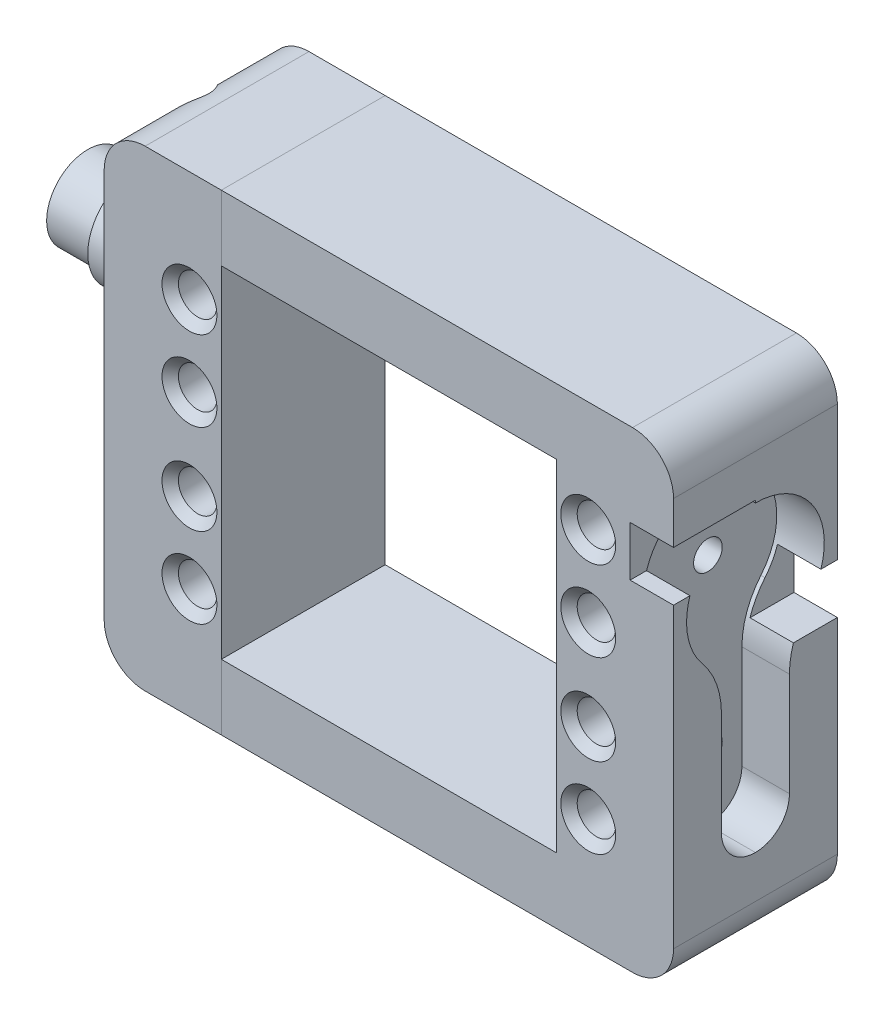
SolidWorks part; units mm, degrees
material "ABS"
ref_plane "Front Plane" through (0, 0, 0) normal (0, 0, 1) x (1, 0, 0)
ref_plane "Top Plane" through (0, 0, 0) normal (0, 1, 0) x (1, 0, 0)
ref_plane "Right Plane" through (0, 0, 0) normal (1, 0, 0) x (0, 0, -1)
sketch "Sketch1" plane through (0, 0, 0) normal (1, 0, 0) x (0, 0, -1)
  line L1 (-10, 10) -> (10, 10)
  line L2 (-10, 10) -> (-10, -10)
  line L3 (-10, -10) -> (10, -10)
  line L4 (10, 10) -> (10, -10)
  line L5 (-10, 10) -> (10, -10) construction
  line L6 (-10, -10) -> (10, 10) construction
  point P0 (0, 0)
  dimension "D1" = 20
  dimension "D2" = 20
extrude "Boss-Extrude1" add sketch "Sketch1" along normal blind 20
sketch "Sketch2" plane through (20, 0, 0) normal (1, 0, 0) x (0, 0, -1)
  line L1 (-10, 35) -> (10, 35)
  line L2 (-10, 35) -> (-10, -35)
  line L3 (-10, -35) -> (10, -35)
  line L4 (10, 35) -> (10, -35)
  line L5 (-10, 35) -> (10, -35) construction
  line L6 (-10, -35) -> (10, 35) construction
  point P0 (0, 0)
  dimension "D1" = 20
  dimension "D2" = 70
extrude "Boss-Extrude2" add sketch "Sketch2" along normal blind 10.3
sketch "Sketch4" plane through (30.3, 0, 0) normal (1, 0, 0) x (0, 0, -1)
  line L0 (0, 7.65) -> (0, 8.1702) construction
  line L1 (7.65, 7.65) -> (-7.65, 7.65) construction
  line L17 (4.15, -26.55) -> (-4.15, -26.55) construction
  line L18 (-7.65, 7.65) -> (7.65, 7.65) construction
  line L22 (-7.65, 7.65) -> (-7.65, -27.55) construction
  line L23 (-7.65, -27.55) -> (7.65, -27.55) construction
  line L24 (7.65, 7.65) -> (7.65, -27.55) construction
  line L25 (-7.65, 7.65) -> (7.65, -27.55) construction
  line L26 (-7.65, -27.55) -> (7.65, 7.65) construction
  line L27 (4.15, -26.55) -> (4.15, -28.55) construction
  line L28 (4.15, -28.55) -> (-4.15, -28.55) construction
  line L29 (-4.15, -26.55) -> (-4.15, -28.55) construction
  line L30 (4.15, -26.55) -> (-4.15, -28.55) construction
  line L31 (4.15, -28.55) -> (-4.15, -26.55) construction
  line L34 (4.15, -28.55) -> (-4.15, -28.55)
  line L35 (-4.15, -28.55) -> (-4.15, -7.3118)
  line L36 (4.15, -28.55) -> (4.15, -7.3118)
  arc A1 (4.15, -6.4265) -> (-4.15, -6.4265) centre (0, 0) ccw construction
  arc A2 (4.15, -7.3118) -> (-4.15, -7.3118) centre (0, 0) ccw
  point P1 (0, -27.55)
  point P7 (0, -13.75)
  point P10 (0, 7.65)
  point P14 (0, -9.95)
  dimension "D1" = 15.3
  dimension "D5" = 2
  dimension "D2" = 15.3
  dimension "D3" = 35.2
  dimension "D4" = 8.3
extrude "Cut-Extrude1" cut sketch "Sketch4" against normal blind 5.8
fillet "Fillet1" radius 4.15 2 edges at (27.4, -28.55, 4.15) (27.4, -28.55, -4.15)
fillet "Fillet2" radius 10 2 edges at (27.4, -7.3118, 4.15) (27.4, -7.3118, -4.15)
sketch "Sketch5" plane through (0, 0, 0) normal (-1, 0, 0) x (0, 0, 1)
  circle A0 centre (0, 0) radius 1.75
  dimension "D1" = 3.5
extrude "Cut-Extrude2" cut sketch "Sketch5" against normal through all
sketch "Sketch6" plane through (24.5, 0, 0) normal (1, 0, 0) x (0, 0, -1)
  line L0 (0, -19.35) -> (0, 0) construction
  line L1 (0, -25.65) -> (0, -23.15) construction
  line L2 (0, -23.15) -> (0, -21.85) construction
  line L3 (0, -21.85) -> (0, -19.35) construction
  line L5 (0, 0) -> (1.164, 0) construction
  line L6 (0, 0) -> (0, -9.35) construction
  line L7 (0, -9.35) -> (1.164, -9.35) construction
  line L8 (1.164, 0) -> (1.164, -9.35) construction
  line L9 (0, 0) -> (1.164, -9.35) construction
  line L10 (0, -9.35) -> (1.164, 0) construction
  circle A0 centre (0, -20.6) radius 1.75
  circle A1 centre (0, -9.35) radius 1.75 construction
  point P11 (0.582, -4.675)
  dimension "D5" = 3.5
  dimension "D6" = 9.35
  dimension "D7" = 3.5
  dimension "D1" = 19.35
  dimension "D2" = 2.5
  dimension "D3" = 1.3
  dimension "D4" = 2.5
extrude "Cut-Extrude3" cut sketch "Sketch6" against normal up to next
sketch "Sketch13" plane through (0, 0, 0) normal (-1, 0, 0) x (0, 0, 1)
  line L1 (-10, 10) -> (10, 10)
  line L2 (-10, 10) -> (-10, -10)
  line L3 (-10, -10) -> (10, -10)
  line L4 (10, 10) -> (10, -10)
extrude "Cut-Extrude9" cut sketch "Sketch13" against normal up to surface (20 mm away) up to face at (20, 22.5, 0)
sketch "Sketch29" plane through (30.3, 0, 0) normal (1, 0, 0) x (0, 0, -1)
  line L0 (0, 0) -> (0, 2.6) construction
  line L1 (15.1094, -8.7) -> (15.1094, -2.6)
  line L2 (0, 2.6) -> (-15.1094, 2.6)
  line L4 (0, 2.6) -> (0, 3.8)
  line L5 (0, 3.8) -> (0, 7.5)
  line L6 (0, 7.5) -> (0, 8.7)
  line L7 (0, 8.7) -> (-15.1094, 8.7)
  line L8 (-15.1094, 8.7) -> (-15.1094, 2.6)
  line L9 (0, -2.6) -> (15.1094, -2.6)
  line L10 (0, -2.6) -> (0, -3.8)
  line L11 (0, -3.8) -> (0, -7.5)
  line L12 (0, -7.5) -> (0, -8.7)
  line L13 (0, -8.7) -> (15.1094, -8.7)
  point P19 (0, 0)
  dimension "D1" = 2.6
  dimension "D2" = 1.2
  dimension "D3" = 3.7
  dimension "D4" = 1.2
  dimension "D5" = 2
extrude "Cut-Extrude18" cut sketch "Sketch29" against normal blind 5.3
sketch "Sketch32" plane through (30.3, 0, 0) normal (1, 0, 0) x (0, 0, -1)
  line L0 (0, -28.55) -> (0, -38.725) construction
  line L1 (10, -35) -> (10, -8.7) construction
  line L2 (-10, -35) -> (10, -35)
  line L3 (-10, -35) -> (-10, -38.725)
  line L4 (-10, -38.725) -> (10, -38.725)
  line L5 (10, -35) -> (10, -38.725)
  dimension "D1" = 10.175
extrude "Boss-Extrude3" add sketch "Sketch32" against normal up to surface (10.3 mm away) up to face at (20, 0, 0)
sketch "Sketch31" plane through (30.3, 0, 0) normal (1, 0, 0) x (0, 0, -1)
  line L2 (0, 8.7) -> (0, 18.875) construction
  line L3 (10, -2.6) -> (10, 35) construction
  line L4 (-10, 35) -> (10, 35)
  line L5 (-10, 35) -> (-10, 18.875)
  line L6 (-10, 18.875) -> (10, 18.875)
  line L7 (10, 35) -> (10, 18.875)
  dimension "D1" = 10.175
extrude "Cut-Extrude19" cut sketch "Sketch31" against normal through all
sketch "Sketch34" plane through (20, 0, 0) normal (-1, 0, 0) x (0, 0, 1)
  line L4 (10, -38.725) -> (10, 18.875)
  line L5 (10, 18.875) -> (-10, 18.875)
  line L6 (-10, 18.875) -> (-10, -38.725)
  line L7 (-10, -38.725) -> (10, -38.725)
  line L8 (10, -38.725) -> (10, 18.875)
  line L9 (10, 18.875) -> (-10, 18.875)
  line L10 (-10, 18.875) -> (-10, -38.725)
  line L11 (-10, -38.725) -> (10, -38.725)
  circle A0 centre (0, -20.6) radius 1.75 construction
  circle A1 centre (0, 0) radius 1.75 construction
  circle A2 centre (0, -20.6) radius 1.75
  circle A3 centre (0, 0) radius 1.75
  dimension "D1" = 0
extrude "Boss-Extrude5" add sketch "Sketch34" along normal blind 4
sketch "Sketch35" plane through (16, 0, 0) normal (-1, 0, 0) x (0, 0, 1)
  line L0 (10, -38.725) -> (10, 18.875) construction
  line L1 (-10, 18.875) -> (10, 18.875)
  line L2 (-10, 18.875) -> (-10, 10.875)
  line L3 (-10, 10.875) -> (10, 10.875)
  line L4 (10, 18.875) -> (10, 10.875)
  line L5 (0, 10.875) -> (0, -30.725) construction
  line L6 (-10, -38.725) -> (10, -38.725)
  line L7 (-10, -38.725) -> (-10, -30.725)
  line L8 (-10, -30.725) -> (10, -30.725)
  line L9 (10, -38.725) -> (10, -30.725)
  dimension "D1" = 41.6
extrude "Boss-Extrude6" add sketch "Sketch35" along normal blind 40.9
sketch "Sketch37" plane through (-24.9, 0, 0) normal (-1, 0, 0) x (0, 0, 1)
  line L1 (-10, 18.875) -> (10, 18.875)
  line L2 (-10, 18.875) -> (-10, -38.725)
  line L3 (-10, -38.725) -> (10, -38.725)
  line L4 (10, 18.875) -> (10, -38.725)
extrude "Boss-Extrude7" add sketch "Sketch37" along normal blind 14.3
sketch "Sketch38" plane through (0, 0, 10) normal (0, 0, 1) x (1, 0, 0)
  line L0 (-24.9, 10.875) -> (-24.9, -9.925) construction
  line L1 (-24.9, -9.925) -> (-24.9, -30.725) construction
  line L2 (-24.9, -30.725) -> (-24.9, 10.875) construction
  line L3 (-24.9, -9.925) -> (-39.2, -9.925) construction
  line L4 (-39.2, -38.725) -> (-39.2, 18.875) construction
  line L5 (-24.9, 0.475) -> (-28.79, 0.475) construction
  line L6 (-28.79, 0.475) -> (-28.79, 5.375) construction
  line L7 (-24.9, 10.875) -> (16, 10.875) construction
  line L8 (-4.45, 10.875) -> (-4.45, -38.725) construction
  line L9 (-39.2, -38.725) -> (30.3, -38.725) construction
  circle A0 centre (-28.79, 5.375) radius 2.35
  circle A1 centre (-28.79, -4.425) radius 2.35
  circle A2 centre (-28.79, -25.225) radius 2.35
  circle A3 centre (-28.79, -15.425) radius 2.35
  circle A4 centre (19.89, 5.375) radius 2.35
  circle A5 centre (19.89, -4.425) radius 2.35
  circle A6 centre (19.89, -15.425) radius 2.35
  circle A7 centre (19.89, -25.225) radius 2.35
  dimension "D4" = 4.7
  dimension "D1" = 41.6
  dimension "D2" = 3.89
  dimension "D3" = 4.9
extrude "Cut-Extrude20" cut sketch "Sketch38" against normal blind 8
chamfer "Chamfer1" distance 1 angle 45 8 edges at (22.24, -25.225, 10) (17.54, -15.425, 10) (22.24, -4.425, 10) (17.54, 5.375, 10) (-26.44, 5.375, 10) (-26.44, -15.425, 10) (-31.14, -25.225, 10) (-31.14, -4.425, 10)
sketch "Sketch41" plane through (16, 0, 0) normal (-1, 0, 0) x (0, 0, 1)
  circle A0 centre (0, 0) radius 3.5
  circle A1 centre (0, -20.6) radius 3.5
  dimension "D1" = 7
  dimension "D2" = 7
extrude "Cut-Extrude23" cut sketch "Sketch41" against normal blind 4
sketch "Sketch42" plane through (-39.2, 0, 0) normal (-1, 0, 0) x (0, 0, 1)
  line L0 (10, -38.725) -> (10, 18.875) construction
  line L1 (-10, -38.725) -> (10, -38.725) construction
  line L2 (-10, -38.725) -> (-10, -30.725) construction
  line L3 (-10, -30.725) -> (10, -30.725) construction
  line L4 (10, -38.725) -> (10, -30.725) construction
  line L5 (-10, -9.925) -> (10, -9.925) construction
  line L6 (-10, 18.875) -> (-10, -38.725) construction
  circle A0 centre (0, -34.725) radius 1.75
  circle A1 centre (0, 14.875) radius 1.75
  point P9 (-10, -34.725)
  dimension "D2" = 3.5
  dimension "D1" = 8
  dimension "D3" = 4
  dimension "D4" = 10
extrude "Cut-Extrude24" cut sketch "Sketch42" against normal blind 22.3
sketch "Sketch43" plane through (-39.2, 0, 0) normal (-1, 0, 0) x (0, 0, 1)
  circle A0 centre (0, 14.875) radius 3.5
  circle A1 centre (0, -34.725) radius 3.5
  dimension "D1" = 7
  dimension "D2" = 7
extrude "Cut-Extrude25" cut sketch "Sketch43" against normal blind 11
fillet "Fillet3" radius 5 4 edges at (-39.2, -38.725, 0) (30.3, -38.725, 0) (30.3, 18.875, 0) (-39.2, 18.875, 0)
sketch "Sketch44" plane through (0, 0, 10) normal (0, 0, 1) x (1, 0, 0)
  line L0 (-24.9, 18.875) -> (-24.9, -38.725)
  line L1 (-34.2, 18.875) -> (25.3, 18.875) construction
  line L2 (-34.2, -38.725) -> (25.3, -38.725) construction
split "Split1" trim tools "Sketch44" bodies to split 171 resulting bodies 172 173
sketch "Sketch45" plane through (-24.9, 0, 0) normal (-1, 0, 0) x (0, 0, 1)
  circle A0 centre (0, 14.875) radius 2.35
  circle A1 centre (0, -34.725) radius 2.35
  dimension "D1" = 4.7
  dimension "D2" = 4.7
extrude "Cut-Extrude26" cut sketch "Sketch45" against normal blind 8
chamfer "Chamfer2" distance 1 angle 45 2 edges at (-24.9, -34.725, 2.35) (-24.9, 14.875, 2.35)
sketch "Sketch46" plane through (-39.2, 0, 0) normal (-1, 0, 0) x (0, 0, 1)
  circle A1 centre (0, 0) radius 5.025
  dimension "D1" = 10.05
extrude "Boss-Extrude8" add sketch "Sketch46" along normal blind 12
sketch "Sketch50" plane through (-39.2, 0, 0) normal (-1, 0, 0) x (0, 0, 1)
  circle A0 centre (0, 0) radius 6
  dimension "D1" = 12
extrude "Boss-Extrude9" add sketch "Sketch50" along normal blind 6
fillet "Fillet6" radius 3 1 edges at (-39.2, 0, 6)
mirror "Mirror1" [suppressed]
delete or keep bodies "Body-Delete/Keep 1" [suppressed] type delete bodies bodies 177 174
sketch "Sketch47" plane through (0, 0, 10) normal (0, 0, 1) x (1, 0, 0)
  line L0 (19.89, 5.375) -> (19.89, -4.425)
  line L1 (19.89, 0.475) -> (28.8988, 0.475)
sketch "Sketch48" plane through (24.5, 0, 0) normal (1, 0, 0) x (0, 0, -1)
  line L0 (0, 0) -> (-13.129, 0)
  line L1 (-10, 8.725) -> (-10, 2.025) construction
sketch "Sketch49" plane through (0, 0, 10) normal (0, 0, 1) x (1, 0, 0)
  line L0 (24.5491, 0) -> (24.5491, 0.475)
  line L1 (19.89, 0.475) -> (28.8988, 0.475) construction
other "Save Bodies1"
